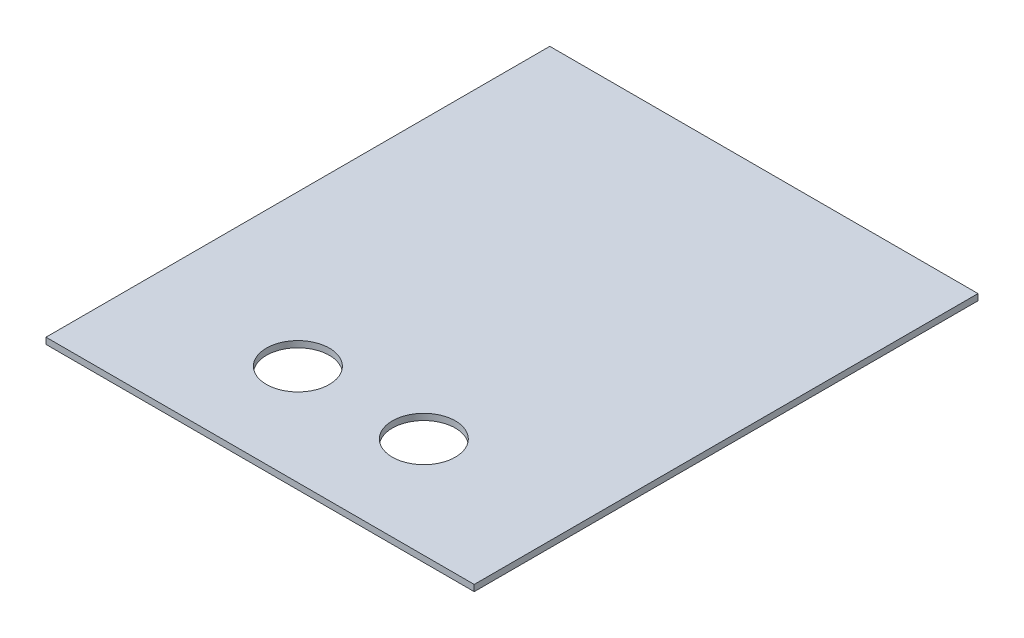
SolidWorks part; units mm, degrees
ref_plane "Front Plane" through (0, 0, 0) normal (0, 0, 1) x (1, 0, 0)
ref_plane "Top Plane" through (0, 0, 0) normal (0, 1, 0) x (1, 0, 0)
ref_plane "Right Plane" through (0, 0, 0) normal (1, 0, 0) x (0, 0, -1)
sketch "Sketch1" plane through (0, 0, 0) normal (0, 1, 0) x (1, 0, 0)
  line L1 (0, 0) -> (215.9, 0)
  line L2 (0, 0) -> (0, 254)
  line L3 (0, 254) -> (215.9, 254)
  line L4 (215.9, 0) -> (215.9, 254)
  dimension "D1" = 215.9
  dimension "D2" = 254
extrude "Boss-Extrude1" add sketch "Sketch1" along normal blind 3.175
sketch "Sketch2" plane through (0, 3.175, 0) normal (0, 1, 0) x (1, 0, 0)
  line L0 (139.7, 50.8) -> (76.2, 50.8) construction
  line L2 (139.7, 50.8) -> (215.9, 50.8) construction
  line L3 (215.9, 0) -> (215.9, 254) construction
  line L4 (76.2, 50.8) -> (0, 50.8) construction
  line L5 (0, 0) -> (215.9, 0) construction
  line L6 (0, 254) -> (0, 0) construction
  circle A0 centre (139.7, 50.8) radius 15.875
  circle A1 centre (76.2, 50.8) radius 15.875
  dimension "D1" = 31.75
  dimension "D2" = 50.8
  dimension "D3" = 63.5
extrude "Cut-Extrude1" cut sketch "Sketch2" against normal through all
